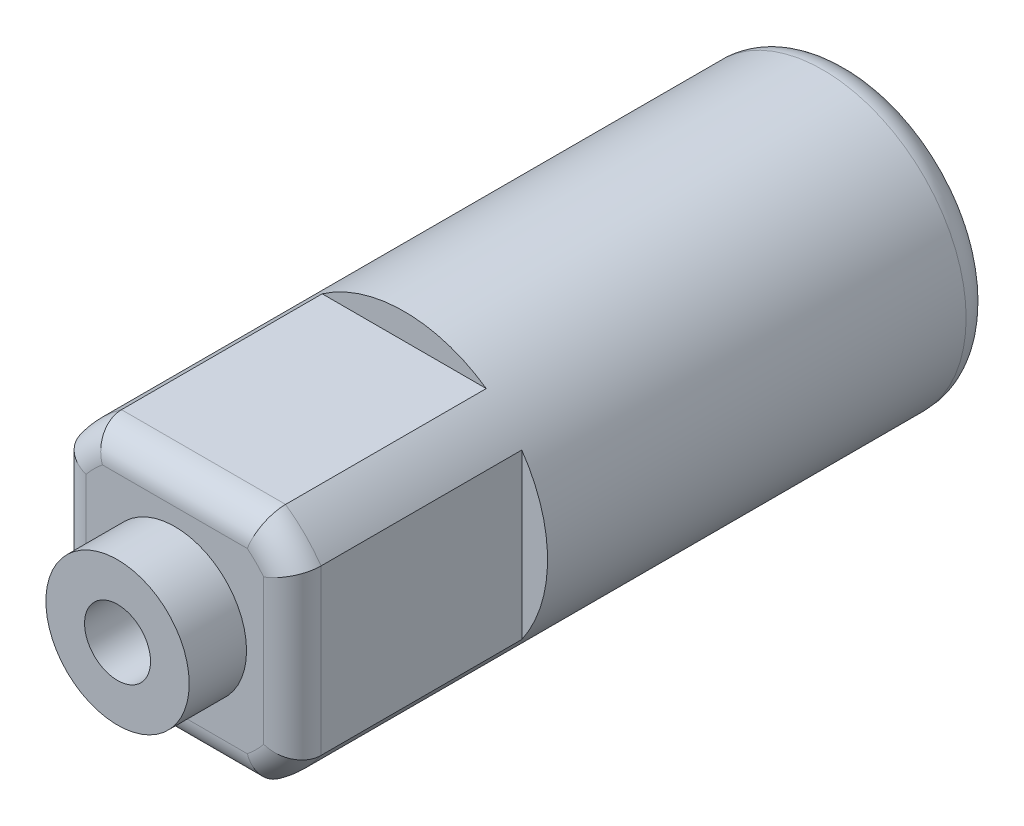
SolidWorks part; units mm, degrees
ref_plane "Přední rovina" through (0, 0, 0) normal (0, 0, 1) x (1, 0, 0)
ref_plane "Horní rovina" through (0, 0, 0) normal (0, 1, 0) x (1, 0, 0)
ref_plane "Pravá rovina" through (0, 0, 0) normal (1, 0, 0) x (0, 0, -1)
sketch "Skica1" plane through (0, 0, 0) normal (0, 0, 1) x (1, 0, 0)
  circle A0 centre (0, 0) radius 5
  dimension "D1" = 10
extrude "Přidat vysunutím1" add sketch "Skica1" along normal blind 23.6
sketch "Skica2" plane through (0, 0, 23.6) normal (0, 0, -1) x (-1, 0, 0)
  line L1 (-4.1, -4.1) -> (4.1, -4.1)
  line L2 (-4.1, -4.1) -> (-4.1, 4.1)
  line L3 (-4.1, 4.1) -> (4.1, 4.1)
  line L4 (4.1, -4.1) -> (4.1, 4.1)
  line L5 (-4.1, -4.1) -> (4.1, 4.1) construction
  line L6 (-4.1, 4.1) -> (4.1, -4.1) construction
  point P0 (0, 0)
  dimension "D1" = 8.2
extrude "Odebrat vysunutím1" cut sketch "Skica2" along normal blind 8 flip side to cut
sketch "Skica3" plane through (0, 0, 23.6) normal (0, 0, 1) x (1, 0, 0)
  circle A0 centre (0, 0) radius 2.5
  dimension "D1" = 5
extrude "Přidat vysunutím2" add sketch "Skica3" along normal blind 2
sketch "Skica4" plane through (0, 0, 25.6) normal (0, 0, 1) x (1, 0, 0)
  circle A0 centre (0, 0) radius 1.15
  dimension "D1" = 2.3
extrude "Odebrat vysunutím2" cut sketch "Skica4" against normal blind 11
fillet "Zaoblit1" radius 1 10 edges at (5, 0, 0) (-3.5355, 3.5355, 23.6) (0, 4.1, 23.6) (3.5355, 3.5355, 23.6) (4.1, 0, 23.6) (3.5355, -3.5355, 23.6) (0, -4.1, 23.6) (-3.5355, -3.5355, 23.6) (-4.1, 0, 23.6) (1.15, 0, 14.6)
